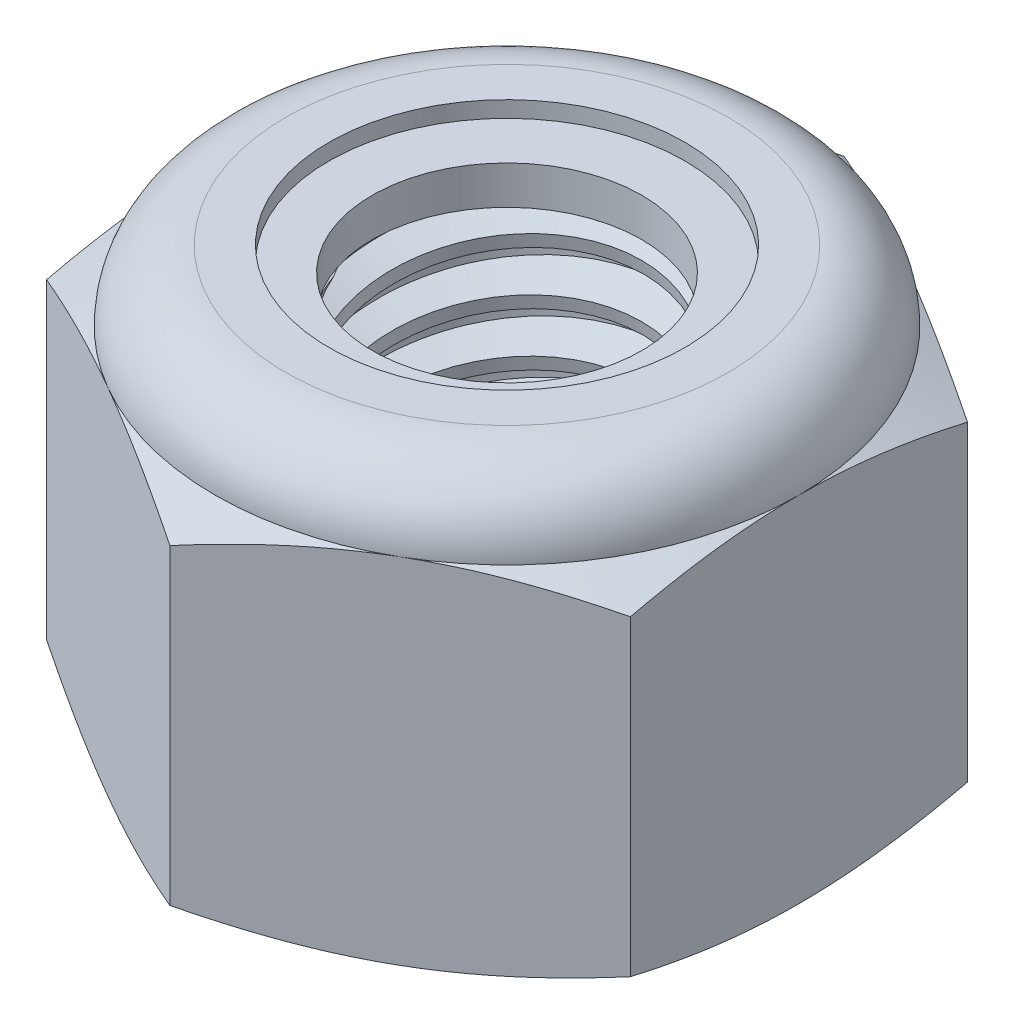
SolidWorks part; units mm, degrees
material "Alloy Steel "
ref_plane "Front" through (0, 0, 0) normal (0, 0, 1) x (1, 0, 0)
ref_plane "Top" through (0, 0, 0) normal (0, 1, 0) x (1, 0, 0)
ref_plane "Right" through (0, 0, 0) normal (1, 0, 0) x (0, 0, -1)
sketch "Sketch1" plane through (0, 0, 0) normal (0, 1, 0) x (1, 0, 0)
  line L1 (0, 3.1754) -> (-2.75, 1.5877)
  line L2 (-2.75, 1.5877) -> (-2.75, -1.5877)
  line L3 (-2.75, -1.5877) -> (0, -3.1754)
  line L4 (0, -3.1754) -> (2.75, -1.5877)
  line L5 (2.75, -1.5877) -> (2.75, 1.5877)
  line L6 (2.75, 1.5877) -> (0, 3.1754)
  circle A0 centre (0, 0) radius 2.75 construction
  dimension "Hex Flats" = 5.5
extrude "Extrude1" add sketch "Sketch1" along normal blind 4
sketch "Sketch2" plane through (0, 0, 0) normal (1, 0, 0) x (0, 0, -1)
  line L0 (-1.5, 0) -> (-1.5, 4) construction
  line L1 (0, 0) -> (1.5, 0)
  line L2 (0, 0) -> (0, 4)
  line L3 (0, 4) -> (1.5, 4)
  line L4 (1.5, 0) -> (1.5, 4)
  line L5 (-1.5877, 4) -> (1.5877, 4) construction
  line L7 (0, -1.5) -> (0, 0) construction
  dimension "Thread Dia" = 3
revolve "Revolve1" add sketch "Sketch2" angle 360 about L7
sketch "Sketch3" plane through (0, 0, 0) normal (1, 0, 0) x (0, 0, -1)
  line L0 (1.5, 4) -> (-1.5, 4) construction
  line L1 (-1.5, 4) -> (-1.5, 3.5) construction
  line L2 (-1.5, 3.5) -> (1.5, 4) construction
  line L3 (1.5, 4) -> (1.5103, 3.9384) construction
  line L4 (1.5103, 3.9384) -> (1.5822, 3.5068)
  line L5 (1.5822, 3.5068) -> (1.2896, 3.6164)
  line L6 (1.2896, 3.6164) -> (1.269, 3.7397)
  line L7 (1.269, 3.7397) -> (1.5103, 3.9384)
  line L8 (1.2793, 3.6781) -> (1.5462, 3.7226) construction
  line L9 (1.5, 4) -> (1.5, 3.7149) construction
  line L10 (1.5, 3.7149) -> (-1.5, 3.2149) construction
  line L11 (-1.5, 3.2149) -> (-1.5, 3.5) construction
  line L12 (-0.0892, 4) -> (0.0892, 2.9297) construction
  line L13 (-1.5, 0) -> (-1.5, 4) construction
  line L14 (0, 4) -> (1.5, 4) construction
  line L15 (1.5, 0) -> (1.5, 4) construction
  point P13 (0, 3.4649)
  dimension "D1" = 0.0625
  dimension "D2" = 0.125
  dimension "Thread Pitch" = 0.5
  dimension "D4" = 60
  dimension "D5" = 0.5
revolve "Cut-Revolve1" cut sketch "Sketch3" angle 360 about L12
pattern_linear "LPattern1" count 8 spacing 0.5 along (0, -1, 0) count 2 spacing 0.5 along (0, 1, 0) of "Cut-Revolve1"
sketch "Sketch4" plane through (0, 0, 0) normal (1, 0, 0) x (0, 0, -1)
  line L0 (0, 4) -> (1.5, 4)
  line L1 (1.5, 4) -> (1.269, 3.8923)
  line L2 (1.269, 3.8923) -> (1.269, 0.1077)
  line L3 (1.269, 0.1077) -> (1.5, 0)
  line L4 (1.5, 0) -> (0, 0)
  line L5 (0, 0) -> (0, 4)
  line L6 (1.5, 0) -> (1.5, 4) construction
  line L7 (0, 4) -> (1.5, 4) construction
  line L8 (0, 0) -> (1.5, 0) construction
  line L9 (0, 0) -> (0, 4) construction
  line L10 (0, 4) -> (0, 4.2549) construction
  dimension "D1" = 25
revolve "Cut-Revolve2" cut sketch "Sketch4" angle 360 about L10
combine bodies "Combine1" operation type subtract main body 112 bodies to subtract 111
sketch "Sketch5" plane through (0, 0, 0) normal (1, 0, 0) x (0, 0, -1)
  line L0 (0, 0) -> (2.75, 0)
  line L1 (2.75, 0) -> (3.1754, 0.1984)
  line L2 (3.1754, 0.1984) -> (3.1754, 3.135)
  line L3 (3.1754, 3.135) -> (2.75, 3.3333)
  line L4 (2.0833, 4) -> (2.0833, 5.27)
  line L5 (2.0833, 5.27) -> (4.4454, 5.27)
  line L6 (4.4454, 5.27) -> (4.4454, -1.27)
  line L7 (4.4454, -1.27) -> (0, -1.27)
  line L8 (0, -1.27) -> (0, 0)
  line L9 (2.75, 3.3333) -> (2.75, 0) construction
  line L10 (0, 0) -> (1.5, 0) construction
  line L13 (3.1754, 1.6667) -> (4.4454, 1.6667) construction
  line L14 (3.1754, 4) -> (3.1754, 0) construction
  line L15 (0, 0) -> (0, 5.27) construction
  line L20 (0, 5.27) -> (2.0833, 5.27) construction
  line L22 (0, 4) -> (1.5, 4) construction
  arc A0 (2.75, 3.3333) -> (2.0833, 4) centre (2.0833, 3.3333) ccw
  dimension "D1" = 25
  dimension "D2" = 1.27
  dimension "D3" = 4
  dimension "D4" = 0.6667
revolve "Cut-Revolve3" cut sketch "Sketch5" angle 360 about L15
sketch "Sketch6" plane through (0, 0, 0) normal (1, 0, 0) x (0, 0, -1)
  line L0 (0, 3.3333) -> (2.5976, 3.3333)
  line L1 (2.0833, 3.8476) -> (1.6762, 3.8476)
  line L2 (0, 5.27) -> (0, 3.3333)
  line L3 (1.6762, 5.27) -> (0, 5.27)
  line L4 (0, 5.27) -> (2.0833, 5.27) construction
  line L5 (0, 0) -> (0, 5.27) construction
  line L6 (0, 5.27) -> (0, 44.323) construction
  line L7 (1.6762, 3.8476) -> (1.6762, 5.27)
  line L8 (2.0833, 4) -> (2.0833, 3.8476) construction
  line L9 (1.6762, 3.8476) -> (1.269, 3.8476) construction
  line L10 (1.269, 3.8476) -> (1.269, 3.8923) construction
  arc A0 (2.5976, 3.3333) -> (2.0833, 3.8476) centre (2.0833, 3.3333) ccw
  arc A1 (2.75, 3.3333) -> (2.0833, 4) centre (2.0833, 3.3333) ccw construction
  dimension "D1" = 0.1524
revolve "Cut-Revolve4" cut sketch "Sketch6" angle 360 about L6
sketch "Sketch7" plane through (0, 0, 0) normal (1, 0, 0) x (0, 0, -1)
  line L0 (1.269, 3.4095) -> (2.5147, 3.4095)
  line L1 (2.0833, 3.7714) -> (1.269, 3.7714)
  line L2 (1.269, 3.7714) -> (1.269, 3.4095)
  line L3 (1.269, 3.4095) -> (0, 3.4095) construction
  line L4 (0, 3.4095) -> (0, 3.7714) construction
  line L5 (0, 3.7714) -> (1.269, 3.7714) construction
  line L6 (1.269, 3.4095) -> (1.269, 3.3333) construction
  line L7 (0, 3.3333) -> (2.5976, 3.3333) construction
  line L8 (2.0833, 3.7714) -> (2.0833, 3.8476) construction
  arc A0 (2.5147, 3.4095) -> (2.0833, 3.7714) centre (2.0833, 3.3333) ccw
  arc A2 (2.5976, 3.3333) -> (2.0833, 3.8476) centre (2.0833, 3.3333) ccw construction
  dimension "D1" = 0.0762
revolve "Revolve2" add sketch "Sketch7" angle 360 about L4
ref_axis "Axe1" through (0, 4.2048, 0) along (0, -1, 0)
equation "\"D1@Sketch3\"=\"Thread Pitch@Sketch3\"/8"
equation "\"D2@Sketch3\"=\"Thread Pitch@Sketch3\"/4"
equation "\"D5@Sketch3\"=\"Thread Pitch@Sketch3\""
equation "\"D4@LPattern1\"=\"Thread Pitch@Sketch3\""
equation "\"D3@LPattern1\"=\"Thread Pitch@Sketch3\""
equation "\"D1@LPattern1\"=\"Height@Extrude1\"/\"Thread Pitch@Sketch3\""
equation "\"D4@Sketch5\"=\"Height@Extrude1\"/6"
